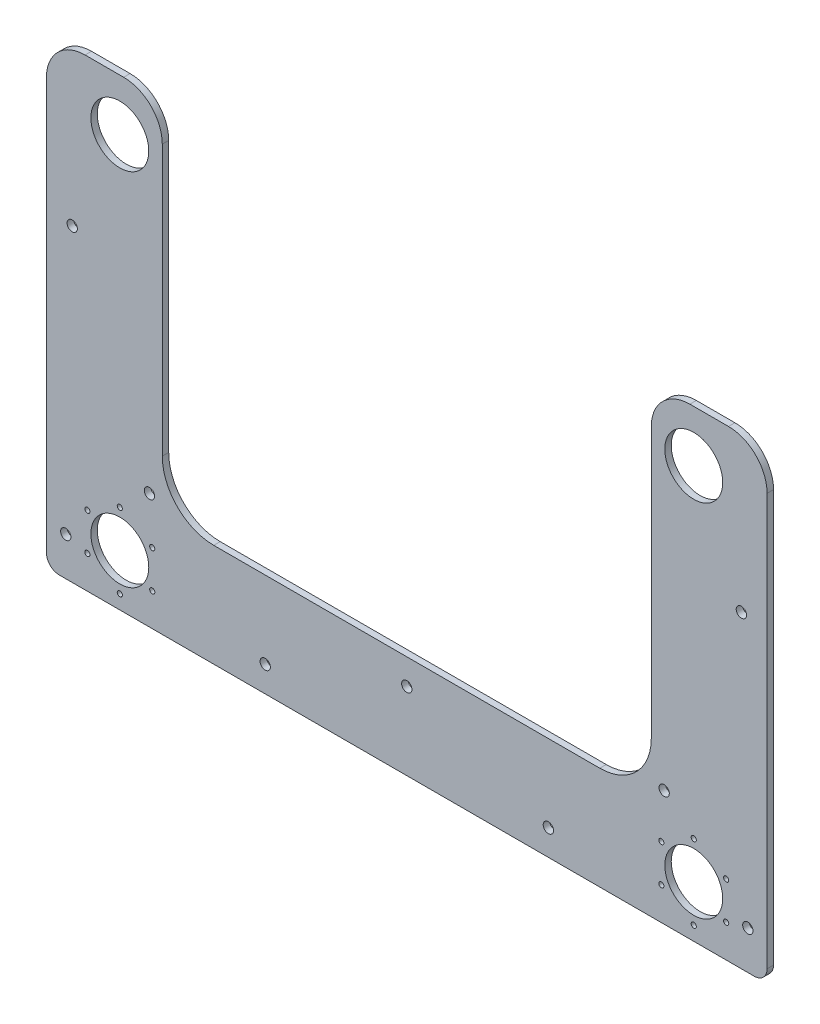
SolidWorks part; units mm, degrees
ref_plane "Front Plane" through (0, 0, 0) normal (0, 0, 1) x (1, 0, 0)
ref_plane "Top Plane" through (0, 0, 0) normal (0, 1, 0) x (1, 0, 0)
ref_plane "Right Plane" through (0, 0, 0) normal (1, 0, 0) x (0, 0, -1)
sketch "Sketch1" plane through (0, 0, 0) normal (0, 0, 1) x (1, 0, 0)
  line L5 (120.65, -152.4) -> (120.65, -6.35)
  line L6 (127, 0) -> (171.45, 0) construction
  line L7 (177.8, -6.35) -> (177.8, -222.25)
  line L10 (0, -206.2199) -> (0, -63.6275) construction
  line L11 (-54.9244, 0) -> (300.6756, 0) construction
  line L13 (12.7, -177.8) -> (95.25, -177.8)
  line L14 (12.7, -228.6) -> (171.45, -228.6)
  line L15 (141.605, -25.4) -> (141.605, -84.2822) construction
  line L16 (141.605, -25.4) -> (141.605, -127) construction
  line L17 (-141.605, -25.4) -> (-141.605, -203.2) construction
  line L18 (-141.605, -25.4) -> (-141.605, -127) construction
  line L19 (-141.605, -19.05) -> (-141.605, -77.9322) construction
  line L20 (141.605, -25.4) -> (141.605, -203.2) construction
  line L22 (-120.65, -152.4) -> (-120.65, -6.35)
  line L23 (-12.7, -177.8) -> (-95.25, -177.8)
  line L24 (-12.7, -228.6) -> (-171.45, -228.6)
  line L25 (-177.8, -6.35) -> (-177.8, -222.25)
  line L26 (-12.7, -177.8) -> (12.7, -177.8)
  line L27 (-12.7, -228.6) -> (12.7, -228.6)
  line L28 (-177.8, -6.35) -> (-177.8, 6.35)
  line L29 (-165.1, 19.05) -> (-133.35, 19.05)
  line L30 (-120.65, 6.35) -> (-120.65, -6.35)
  line L31 (120.65, 6.35) -> (120.65, -6.35)
  line L32 (177.8, -6.35) -> (177.8, 6.35)
  line L33 (165.1, 19.05) -> (133.35, 19.05)
  arc A0 (95.25, -177.8) -> (120.65, -152.4) centre (95.25, -152.4) ccw
  arc A4 (120.65, -6.35) -> (127, 0) centre (127, -6.35) cw construction
  circle A8 centre (141.605, -25.4) radius 14.2875
  circle A9 centre (141.605, -25.4) radius 38.1 construction
  arc A10 (177.8, -6.35) -> (171.45, 0) centre (171.45, -6.35) ccw construction
  arc A11 (171.45, -228.6) -> (177.8, -222.25) centre (171.45, -222.25) ccw
  arc A14 (141.605, -82.55) -> (120.9214, -78.6758) centre (141.605, -25.4) ccw construction
  arc A15 (-141.605, -82.55) -> (-120.9214, -78.6758) centre (-141.605, -25.4) cw construction
  circle A16 centre (-141.605, -25.4) radius 38.1 construction
  circle A17 centre (-141.605, -25.4) radius 14.2875
  arc A19 (-95.25, -177.8) -> (-120.65, -152.4) centre (-95.25, -152.4) cw
  circle A20 centre (141.605, -127) radius 38.1 construction
  circle A21 centre (-141.605, -127) radius 38.1 construction
  arc A23 (-171.45, -228.6) -> (-177.8, -222.25) centre (-171.45, -222.25) cw
  circle A24 centre (-141.605, -203.2) radius 14.2875
  circle A25 centre (-141.605, -184.7225) radius 1.27
  circle A26 centre (-125.603, -193.9612) radius 1.27
  circle A27 centre (-125.603, -212.4388) radius 1.27
  circle A28 centre (-141.605, -221.6775) radius 1.27
  circle A29 centre (-157.607, -212.4388) radius 1.27
  circle A30 centre (-157.607, -193.9612) radius 1.27
  circle A31 centre (157.607, -212.4388) radius 1.27
  circle A32 centre (157.607, -193.9612) radius 1.27
  circle A33 centre (141.605, -184.7225) radius 1.27
  circle A34 centre (125.603, -193.9612) radius 1.27
  circle A35 centre (125.603, -212.4388) radius 1.27
  circle A36 centre (141.605, -221.6775) radius 1.27
  circle A37 centre (141.605, -203.2) radius 14.2875
  circle A39 centre (-69.85, -215.9) radius 2.54
  circle A40 centre (69.85, -215.9) radius 2.54
  circle A42 centre (0, -190.5) radius 2.54
  circle A43 centre (-127, -171.45) radius 2.54
  arc A44 (-133.35, 19.05) -> (-120.65, 6.35) centre (-133.35, 6.35) cw
  arc A45 (-177.8, 6.35) -> (-165.1, 19.05) centre (-165.1, 6.35) cw
  arc A46 (133.35, 19.05) -> (120.65, 6.35) centre (133.35, 6.35) ccw
  arc A47 (177.8, 6.35) -> (165.1, 19.05) centre (165.1, 6.35) ccw
  circle A50 centre (-149.225, 6.35) radius 2.54
  circle A51 centre (127, -171.45) radius 2.54
  circle A53 centre (149.225, 6.35) radius 2.54
  circle A54 centre (-168.275, -209.55) radius 2.54
  circle A56 centre (168.275, -209.55) radius 2.54
  circle A58 centre (-165.1, -76.2) radius 2.54
  circle A59 centre (165.1, -76.2) radius 2.54
  point P2 (177.8, -44.45)
  point P18 (177.8, 0)
  point P23 (177.8, -228.6)
  point P24 (177.8, -228.6)
  point P31 (177.8, 0)
  point P48 (-177.8, 0)
  point P49 (-177.8, -228.6)
  point P51 (-177.8, -44.45)
  point P78 (-141.605, -203.2)
  dimension "D6" = 25.4
  dimension "D7" = 6.35
  dimension "D8" = 6.35
  dimension "D9" = 177.8
  dimension "D10" = 28.575
  dimension "D12" = 76.2
  dimension "D13" = 57.15
  dimension "D15" = 28.575
  dimension "D18" = 76.2
  dimension "D21" = 2.54
  dimension "D29" = 9.525
  dimension "D32" = 5.08
  dimension "D35" = 5.08
  dimension "D37" = 5.08
  dimension "D40" = 12.7
  dimension "D43" = 5.08
  dimension "D45" = 12.7
  dimension "D30" = 5.08
  dimension "D41" = 5.08
  dimension "D2" = 120.65
  dimension "D3" = 177.8
  dimension "D4" = 228.6
  dimension "D5" = 177.8
  dimension "D11" = 20.955
  dimension "`" = 25.4
  dimension "D14" = 57.15
  dimension "D16" = 184.15
  dimension "D17" = 101.6
  dimension "D19" = 25.4
  dimension "D20" = 107.95
  dimension "D22" = 0
  dimension "D23" = 18.4775
  dimension "D25" = 6.9225
  dimension "D26" = 19.05
  dimension "D27" = 25.4
  dimension "D28" = 25.4
  dimension "D31" = 95.25
  dimension "D33" = 12.7
  dimension "D34" = 12.7
  dimension "D36" = 12.7
  dimension "D38" = 57.15
  dimension "D39" = 19.05
  dimension "D42" = 6.35
  dimension "D44" = 28.575
  dimension "D24" = 6
extrude "Boss-Extrude3" add sketch "Sketch1" along normal blind 3.175
sketch "Sketch2" plane through (0, 0, 3.175) normal (0, 0, 1) x (1, 0, 0)
  line L0 (-133.35, 19.05) -> (-165.1, 19.05) construction
  line L1 (-177.8, 19.05) -> (177.8, 19.05)
  line L2 (-177.8, 19.05) -> (-177.8, 0)
  line L3 (-177.8, 0) -> (177.8, 0)
  line L4 (177.8, 19.05) -> (177.8, 0)
  line L5 (-177.8, 6.35) -> (-177.8, -222.25) construction
  line L6 (177.8, -222.25) -> (177.8, 6.35) construction
  dimension "D1" = 19.05
extrude "Cut-Extrude1" cut sketch "Sketch2" against normal through all
fillet "Fillet1" radius 19.05 4 edges at (177.8, 0, 1.5875) (120.65, 0, 1.5875) (-120.65, 0, 1.5875) (-177.8, 0, 1.5875)
